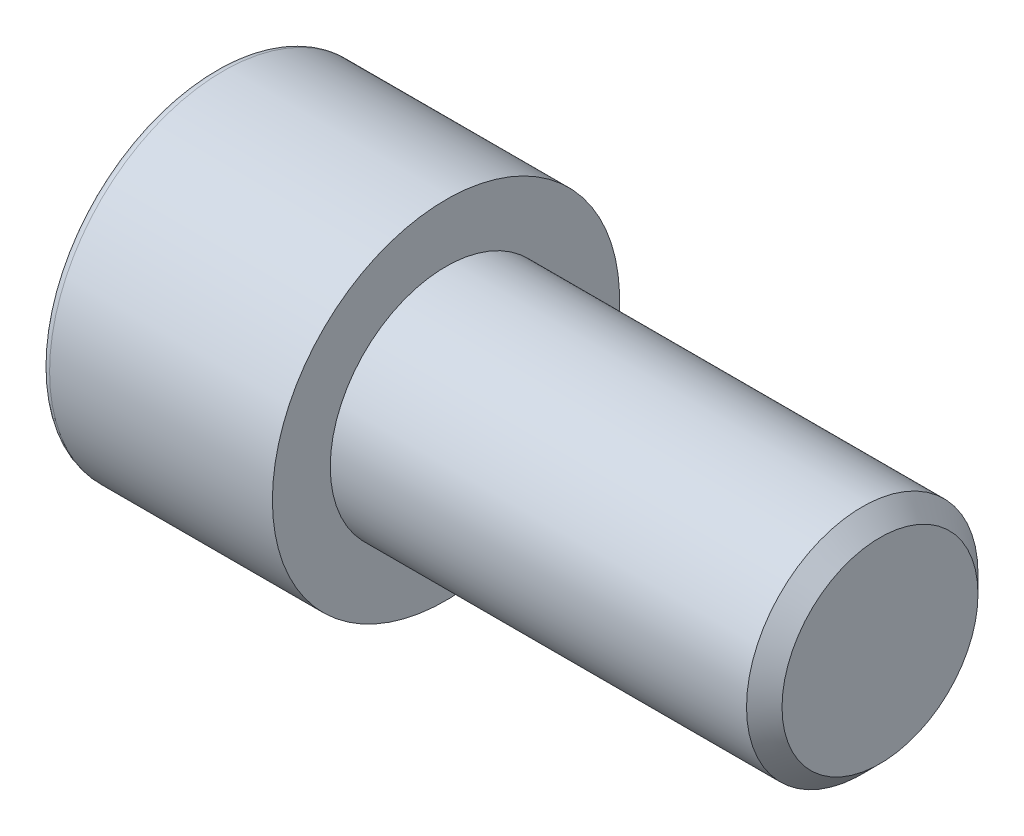
SolidWorks part; units mm, degrees
ref_plane "Płaszczyzna przednia" through (0, 0, 0) normal (0, 0, 1) x (1, 0, 0)
ref_plane "Płaszczyzna górna" through (0, 0, 0) normal (0, 1, 0) x (1, 0, 0)
ref_plane "Płaszczyzna prawa" through (0, 0, 0) normal (1, 0, 0) x (0, 0, -1)
sketch "Szkic1" plane through (0, 0, 0) normal (0, 0, 1) x (1, 0, 0)
  line L0 (0, 0) -> (0, 12)
  line L1 (0, 12) -> (16, 12)
  line L2 (16, 12) -> (16, 0)
  line L3 (16, 0) -> (0, 0)
  line L4 (16, 0) -> (0, 0) construction
revolve "Obrót1" add sketch "Szkic1" angle 360 about L4 reverse direction yes
sketch "Szkic2" plane through (0, 0, 0) normal (0, 0, 1) x (1, 0, 0)
  line L0 (0, 12) -> (0, 11.4)
  line L1 (0.6, 12) -> (0, 12)
  line L2 (16, 0) -> (0, 0) construction
  arc A0 (0, 11.4) -> (0.6, 12) centre (0.6, 11.4) cw
revolve "Wycięcie-obrót1" cut sketch "Szkic2" angle 360 about L2 reverse direction yes
sketch "Szkic3" plane through (0, 0, 0) normal (0, 0, 1) x (1, 0, 0)
  line L0 (16, 0) -> (16, 8)
  line L1 (16, 8) -> (44.773, 8)
  line L2 (44.773, 8) -> (46, 6.773)
  line L3 (46, 6.773) -> (46, 0)
  line L4 (46, 0) -> (16, 0)
  line L5 (46, 0) -> (16, 0) construction
revolve "Obrót2" add sketch "Szkic3" angle 360 about L5 reverse direction yes
cosmetic thread "Oznaczenie gwintu1" parameters "D1"=29.4, "D2"=13.546
sketch "Szkic4" plane through (0, 0, 0) normal (0, 0, 1) x (1, 0, 0)
  line L0 (0, 0) -> (0, 8.5)
  line L1 (0, 8.5) -> (8, 8.5)
  line L2 (8, 8.5) -> (12.9075, 0)
  line L3 (12.9075, 0) -> (0, 0)
  line L4 (12.9075, 0) -> (0, 0) construction
revolve "Wycięcie-obrót2" cut sketch "Szkic4" angle 360 about L4 reverse direction yes
sketch "Szkic5" plane through (0, 0, 0) normal (1, 0, 0) x (0, 0, -1)
  line L0 (-7, 4.0415) -> (-7, -4.0415)
  line L1 (-7, -4.0415) -> (0, -8.0829)
  line L2 (0, -8.0829) -> (7, -4.0415)
  line L3 (7, -4.0415) -> (7, 4.0415)
  line L4 (7, 4.0415) -> (0, 8.0829)
  line L5 (0, 8.0829) -> (-7, 4.0415)
  circle A0 centre (0, 0) radius 9
extrude "Dodanie-wyciągnięcie1" add sketch "Szkic5" along normal blind 12
ref_plane "Płaszczyzna1" through (16, 0, 0) normal (1, 0, 0) x (0, 0, -1)
ref_plane "IP2 XY" through (16, 0, 0) normal (-1, 0, 0) x (0, 0, 1)
ref_plane "IP2 XZ" through (0, 0, 0) normal (0, 1, 0) x (1, 0, 0)
ref_plane "IP2 YZ" through (0, 0, 0) normal (0, 0, -1) x (-1, 0, 0)
ref_axis "IP2 X" through (16, 0, 80.9) along (0, 0, -1)
ref_axis "IP2 Y" through (16, 50, 0) along (0, -1, 0)
ref_axis "IP2 Z" through (-80.9, 0, 0) along (1, 0, 0)
sketch3d "IP2"
  point P0 (16, 0, 0)
